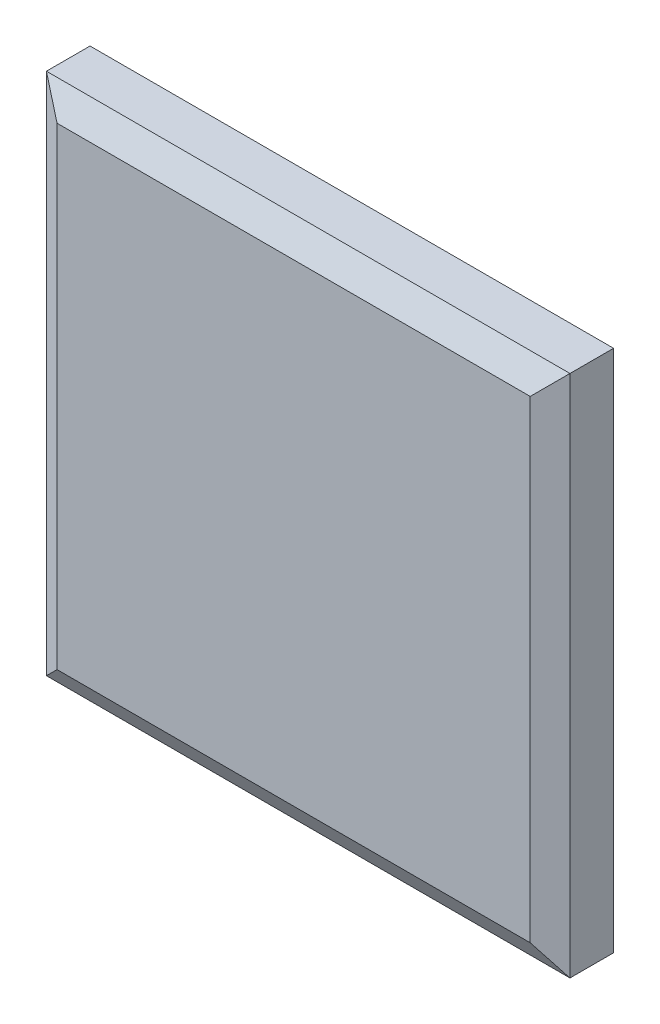
SolidWorks part; units mm, degrees
ref_plane "Plano frontal" through (0, 0, 0) normal (0, 0, 1) x (1, 0, 0)
ref_plane "Plano superior" through (0, 0, 0) normal (0, 1, 0) x (1, 0, 0)
ref_plane "Plano direito" through (0, 0, 0) normal (1, 0, 0) x (0, 0, -1)
sketch "Esboço1" plane through (0, 0, 0) normal (0, 0, 1) x (1, 0, 0)
  line L0 (0, 0) -> (0, 30)
  line L1 (0, 30) -> (15, 30)
  line L2 (15, 30) -> (15, -3)
  line L3 (15, 0) -> (-15, 0)
  line L4 (-15, -3) -> (-15, 30)
  line L5 (-15, 30) -> (0, 30)
  line L6 (0, 31) -> (16, 31)
  line L7 (16, 31) -> (16, -3)
  line L8 (16, -1) -> (-16, -1)
  line L9 (-16, -3) -> (-16, 31)
  line L10 (-16, 31) -> (0, 31)
  line L11 (-18, 33) -> (0, 33)
  line L12 (0, 33) -> (18, 33)
  line L13 (18, 33) -> (18, -3)
  line L14 (18, -3) -> (-18, -3)
  line L15 (-18, -3) -> (-18, 33)
  line L16 (-15, 0) -> (-15, 30) construction
  line L17 (-16, -1) -> (-16, 31) construction
  line L18 (15, 30) -> (15, 0) construction
  line L19 (16, 31) -> (16, -1) construction
  dimension "D1" = 1
  dimension "D2" = 2
extrude "Ressalto-extrusão1" add sketch "Esboço1" along normal blind 1 draft 60 contours L5 L4 L3 L0 | L3 L2 L1 L0 | L10 L9 L8 L4 L5 L1 L2 L7 L6 | L15 L14 L9 L10 L6 L7 L13 L12 L11 | L8 L2 L3 L4 | L14 L7 L8 L2 | L14 L2 L8 L4 | L14 L4 L8 L9 region at (-7.5, 15, 0) region at (7.5, 15, 0) region at (0, -0.5, 0) region at (-7.5, 30.4525, 0) region at (15.5, -2, 0) region at (0, -2, 0) region at (-15.5, -2, 0) region at (16.5091, 15, 0)
extrude "Ressalto-extrusão2" add sketch "Esboço1<4>" against normal blind 3 contours L15 L14 L9 L10 L6 L7 L13 L12 L11 region at (16.5091, 15, 0)
sketch "Esboço1<4>" plane through (0, 0, 0) normal (0, 0, 1) x (1, 0, 0) same geometry as "Esboço1"
sketch "Esboço2" plane through (0, 0, -3) normal (0, 0, -1) x (-1, 0, 0)
  line L0 (16, 11) -> (-16, 11)
  line L1 (18, 33) -> (-18, 33)
  line L2 (18, 33) -> (18, -3)
  line L3 (18, -3) -> (-18, -3)
  line L4 (-18, 33) -> (-18, -3)
  line L5 (16, 4) -> (-16, 4)
  line L6 (16, 11) -> (16, 4)
  line L7 (16, -3) -> (-16, -3)
  line L8 (-16, 4) -> (-16, 11)
  line L10 (18, 11) -> (-18, 11) construction
  line L11 (18, 4) -> (-18, 4) construction
  line M6 (18, -3) -> (18, 33)
  line M7 (18, 33) -> (-18, 33)
  line M8 (-18, 33) -> (-18, -3)
  line M9 (-18, -3) -> (-16, -3)
  line M10 (-16, -3) -> (-16, 31)
  line M11 (-16, 31) -> (16, 31)
  line M12 (16, 31) -> (16, -3)
  line M13 (16, -3) -> (18, -3)
  dimension "D1" = 22
  dimension "D2" = 7
extrude "Ressalto-extrusão3" add sketch "Esboço2" along normal blind 1 draft 60 contours M13 M6 M7 M8 M9 M10 M11 M12 | L0 M12 M11 M10 | L5 L3 M12 M10 region at (-16.5091, 21, -3) region at (0, 21, -3) region at (0, 0.5, -3)
